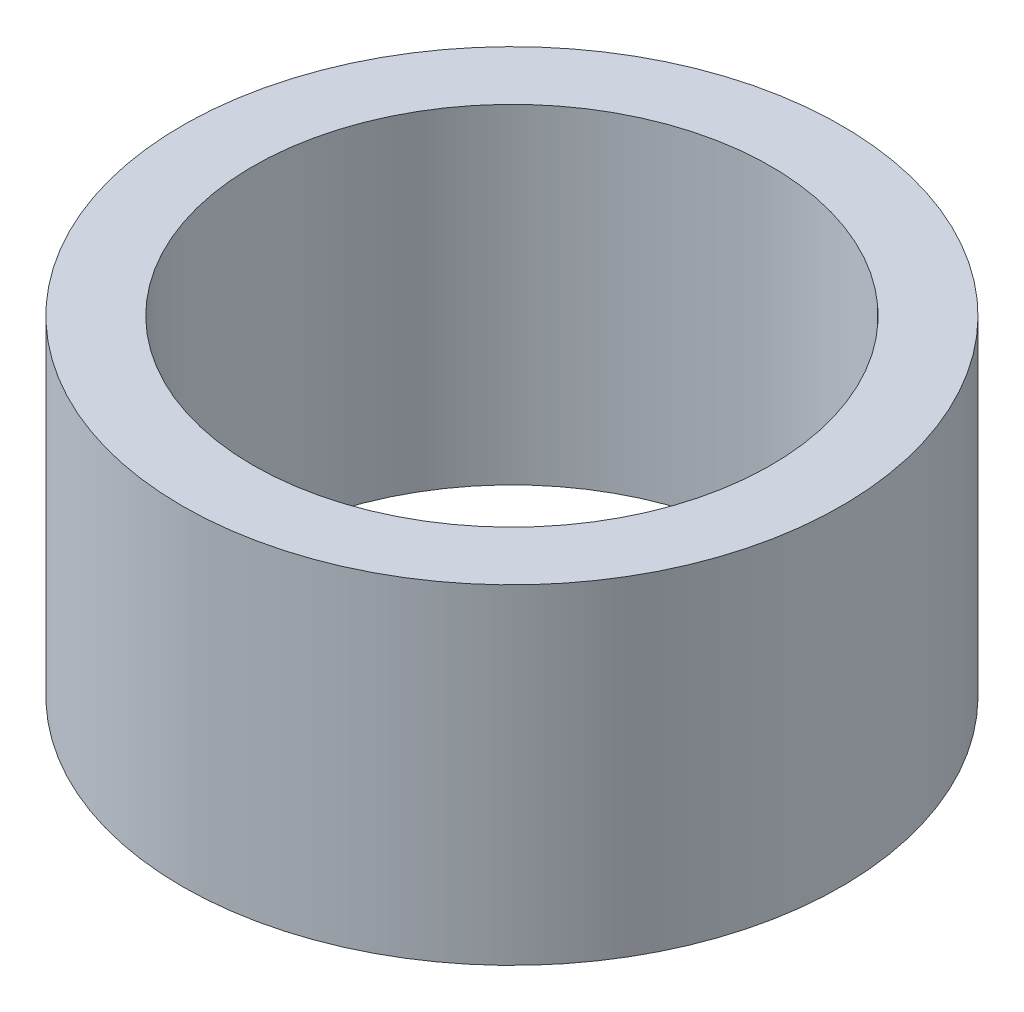
SolidWorks part; units mm, degrees
ref_plane "Plan de face" through (0, 0, 0) normal (0, 0, 1) x (1, 0, 0)
ref_plane "Plan de dessus" through (0, 0, 0) normal (0, 1, 0) x (1, 0, 0)
ref_plane "Plan de droite" through (0, 0, 0) normal (1, 0, 0) x (0, 0, -1)
sketch "Esquisse1" plane through (0, 0, 0) normal (0, 1, 0) x (1, 0, 0)
  circle A0 centre (0, 0) radius 3.5
  circle A1 centre (0, 0) radius 2.75
  dimension "D1" = 7
  dimension "D2" = 0.75
extrude "Boss.-Extru.1" add sketch "Esquisse1" along normal blind 3.5
